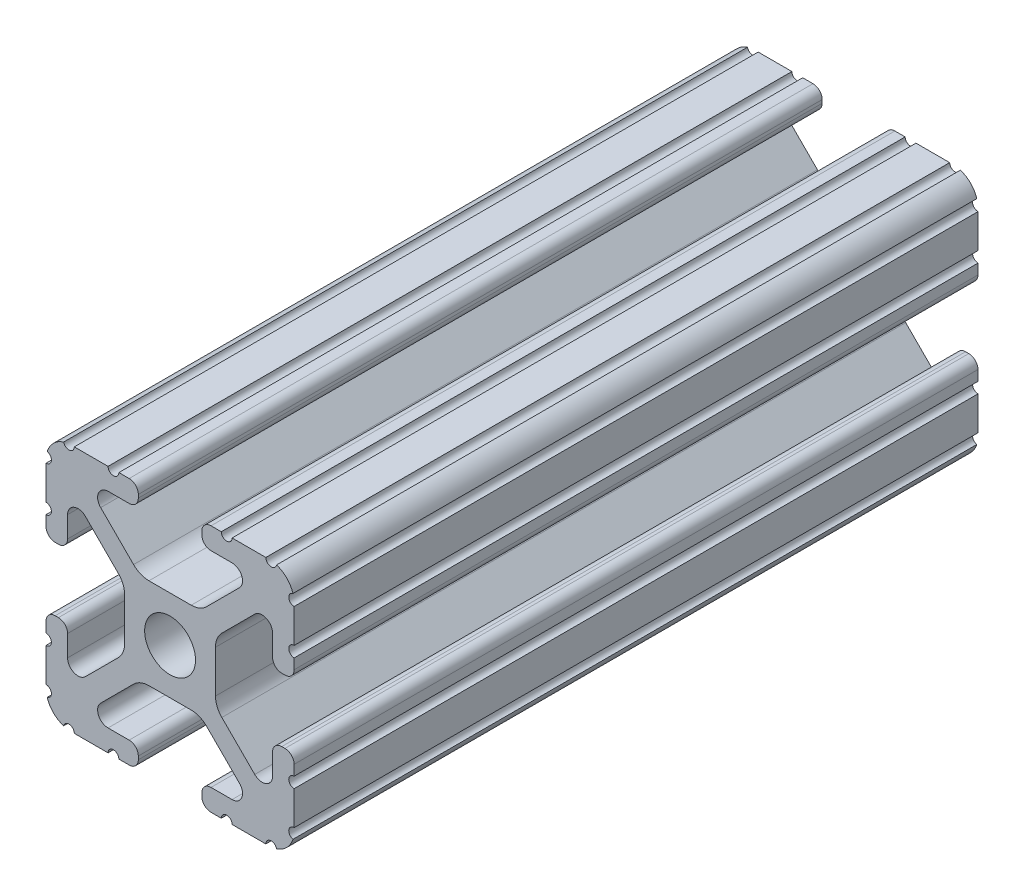
SolidWorks part; units mm, degrees
ref_plane "Front Plane" through (0, 0, 0) normal (0, 0, 1) x (1, 0, 0)
ref_plane "Top Plane" through (0, 0, 0) normal (0, 1, 0) x (1, 0, 0)
ref_plane "Right Plane" through (0, 0, 0) normal (1, 0, 0) x (0, 0, -1)
sketch "Sketch2" plane through (0, 0, 0) normal (0, 0, 1) x (1, 0, 0)
  line L0 (0, 12.7) -> (0, -12.7) construction
  line L1 (-12.7, 0) -> (12.7, 0) construction
  line L2 (3.2512, -12.7) -> (12.7, -12.7)
  line L3 (12.7, -12.7) -> (12.7, -3.2512)
  line L4 (3.2512, -12.7) -> (3.2512, -10.4902)
  line L5 (3.2512, -10.4902) -> (8.9276, -10.4902)
  line L6 (8.9276, -10.4902) -> (3.0856, -4.6482)
  line L7 (0, 0) -> (12.7, -12.7) construction
  line L8 (12.7, -3.2512) -> (10.4902, -3.2512)
  line L9 (10.4902, -3.2512) -> (10.4902, -8.9276)
  line L10 (10.4902, -8.9276) -> (4.6482, -3.0856)
  circle A0 centre (0, 0) radius 2.6035
  arc A1 (6.3485, -10.4902) -> (7.1039, -8.6665) centre (6.3485, -9.4219) ccw construction
  point P8 (0, -4.6482)
  dimension "Center Hole Diameter" = 5.207
  dimension "Rail Height" = 25.4
  dimension "Rail Width" = 25.4
  dimension "T-Slot Width" = 6.5024
  dimension "Slot Inner Width" = 14.8336
  dimension "Thickness" = 2.2098
  dimension "Slot Depth" = 5.842
  dimension "D1" = 2.2098
sketch "Sketch3" plane through (0, 0, 0) normal (1, 0, 0) x (0, 0, -1)
  line L0 (-76.2, -12.7) -> (76.2, -12.7) construction
  line L1 (-68.58, 0) -> (68.58, 0) construction
  dimension "Length" = 152.4
  dimension "D1" = 137.16
sketch "Sketch4" plane through (0, 0, 0) normal (0, 0, 1) x (1, 0, 0)
  line L0 (4.1904, -12.7) -> (10.1173, -12.7)
  line L1 (3.2512, -12.7) -> (12.7, -12.7) construction
  line L2 (3.2512, -12.7) -> (3.2512, -10.4902) construction
  line L3 (3.2512, -10.4902) -> (8.9276, -10.4902) construction
  line L4 (3.2512, -11.4294) -> (3.2512, -11.7608)
  line L5 (4.1904, -10.4902) -> (6.3485, -10.4902)
  line L6 (0, -4.6482) -> (2.164, -4.6482)
  line L7 (8.9276, -10.4902) -> (3.0856, -4.6482) construction
  line L8 (3.7373, -5.2999) -> (7.1039, -8.6665)
  line L9 (12.7, -12.7) -> (12.7, -3.2512) construction
  line L10 (10.4902, -8.9276) -> (4.6482, -3.0856) construction
  line L11 (10.4902, -3.2512) -> (10.4902, -8.9276) construction
  line L12 (10.4902, -6.3485) -> (10.4902, -4.1904)
  line L13 (12.7, -3.2512) -> (10.4902, -3.2512) construction
  line L14 (11.4294, -3.2512) -> (11.7608, -3.2512)
  line L15 (12.7, -4.1904) -> (12.7, -10.1173)
  line L16 (8.6665, -7.1039) -> (5.2999, -3.7373)
  line L17 (4.6482, 0) -> (4.6482, -2.164)
  line L18 (-12.7, 0) -> (12.7, 0) construction
  line L19 (0, -4.6482) -> (0, -2.6035)
  line L20 (0, 12.7) -> (0, -12.7) construction
  line L21 (4.6482, 0) -> (2.6035, 0)
  arc A0 (3.2512, -11.7608) -> (4.1904, -12.7) centre (4.1904, -11.7608) ccw
  arc A2 (3.2512, -11.4294) -> (4.1904, -10.4902) centre (4.1904, -11.4294) cw
  arc A3 (6.3485, -10.4902) -> (7.1039, -8.6665) centre (6.3485, -9.4219) ccw
  arc A4 (2.164, -4.6482) -> (3.7373, -5.2999) centre (2.164, -6.8732) cw
  arc A5 (10.1173, -12.7) -> (12.7, -10.1173) centre (10.1173, -10.1173) ccw
  arc A6 (8.6665, -7.1039) -> (10.4902, -6.3485) centre (9.4219, -6.3485) ccw
  arc A7 (10.4902, -4.1904) -> (11.4294, -3.2512) centre (11.4294, -4.1904) cw
  arc A8 (11.7608, -3.2512) -> (12.7, -4.1904) centre (11.7608, -4.1904) cw
  arc A9 (5.2999, -3.7373) -> (4.6482, -2.164) centre (6.8732, -2.164) cw
  circle A10 centre (0, 0) radius 2.6035 construction
  arc A11 (0, -2.6035) -> (2.6035, 0) centre (0, 0) ccw
  dimension "D1" = 2.5827
  dimension "D2" = 2.225
  dimension "D3" = 0.9392
extrude "Boss-Extrude1" add sketch "Sketch4" along normal mid plane 70
sketch "Sketch5" plane through (0, 0, 0) normal (0, 0, 1) x (1, 0, 0)
  line L0 (3.2512, -12.7) -> (12.7, -12.7) construction
  line L1 (4.1904, -10.4902) -> (6.3485, -10.4902) construction
  line L3 (0, 0) -> (12.7, -12.7) construction
  line L4 (6.3485, -10.4902) -> (6.3485, -12.7) construction
  line L5 (8.9276, -10.4902) -> (3.0856, -4.6482) construction
  circle A0 centre (10.3562, -12.7) radius 0.5524
  circle A1 centre (5.796, -12.7) radius 0.5524
  circle A2 centre (12.7, -10.3562) radius 0.5524
  circle A3 centre (12.7, -5.796) radius 0.5524
  point P10 (5.2694, -10.4902)
  point P12 (9.4219, -6.3485)
  dimension "D1" = 1.1049
extrude "Cut-Extrude1" cut sketch "Sketch5" against normal through all both and the other way through all
mirror "Mirror1" about plane through (0, 0, 0) normal (1, 0, 0) of bodies 137 134
mirror "Mirror2" about plane through (0, 0, 0) normal (0, 1, 0) of bodies 135
sketch "Sketch6" plane through (0, 0, 0) normal (0, 1, 0) x (1, 0, 0)
  line L0 (0, 35) -> (0, 22.3) construction
  line L1 (0, -35) -> (0, -22.3) construction
  line L4 (2.164, 35) -> (-2.164, 35)
  line L5 (-2.164, 35) -> (-2.164, -35)
  line L6 (-2.164, -35) -> (2.164, -35)
  line L7 (2.164, -35) -> (2.164, 35)
  line L8 (2.164, 35) -> (-2.164, 35) construction
  line L9 (-2.164, 35) -> (-2.164, -35) construction
  line L10 (-2.164, -35) -> (2.164, -35) construction
  line L11 (2.164, -35) -> (2.164, 35) construction
  circle A0 centre (0, -22.3) radius 2.555
  circle A1 centre (0, 22.3) radius 2.555
  point P11 (0, -22.3)
  dimension "D2" = 12.7
  dimension "D3" = 5.11
  dimension "D1" = 0
extrude "Cut-Extrude2" cut sketch "Sketch6" against normal through all both and the other way through all
sketch "Sketch7" plane through (0, 0, 0) normal (1, 0, 0) x (0, 0, -1)
  line L0 (-35, 0) -> (-9.6, 0) construction
  line L1 (-35, -2.164) -> (35, -2.164) construction
  line L6 (-35, -2.164) -> (-35, 2.164) construction
  line L7 (-35, 2.164) -> (35, 2.164) construction
  line L8 (35, -2.164) -> (35, 2.164) construction
  line L9 (-35, -2.164) -> (35, 2.164) construction
  line L10 (-35, 2.164) -> (35, -2.164) construction
  line L11 (35, 0) -> (9.6, 0) construction
  circle A2 centre (9.6, 0) radius 2.54
  circle A3 centre (-9.6, 0) radius 2.54
  point P0 (0, 0)
  dimension "D1" = 25.4
  dimension "D2" = 5.08
extrude "Cut-Extrude3" cut sketch "Sketch7" against normal through all both and the other way through all
equation "\"D1@Boss-Extrude1\"=70"
equation "\"D1@Sketch2\"=\"Thickness@Sketch2\""
equation "\"D2@Sketch4\"=\"Slot Inner Width@Sketch2\"*0.15"
equation "\"D1@Sketch4\"=\"D3@Sketch4\"*2.75"
equation "\"D3@Sketch4\"=\"Thickness@Sketch2\"*0.425"
equation "\"D1@Sketch5\"=\"Thickness@Sketch2\"*0.5"
equation "\"D1@Sketch3\"=\"Length@Sketch3\"*0.9"
